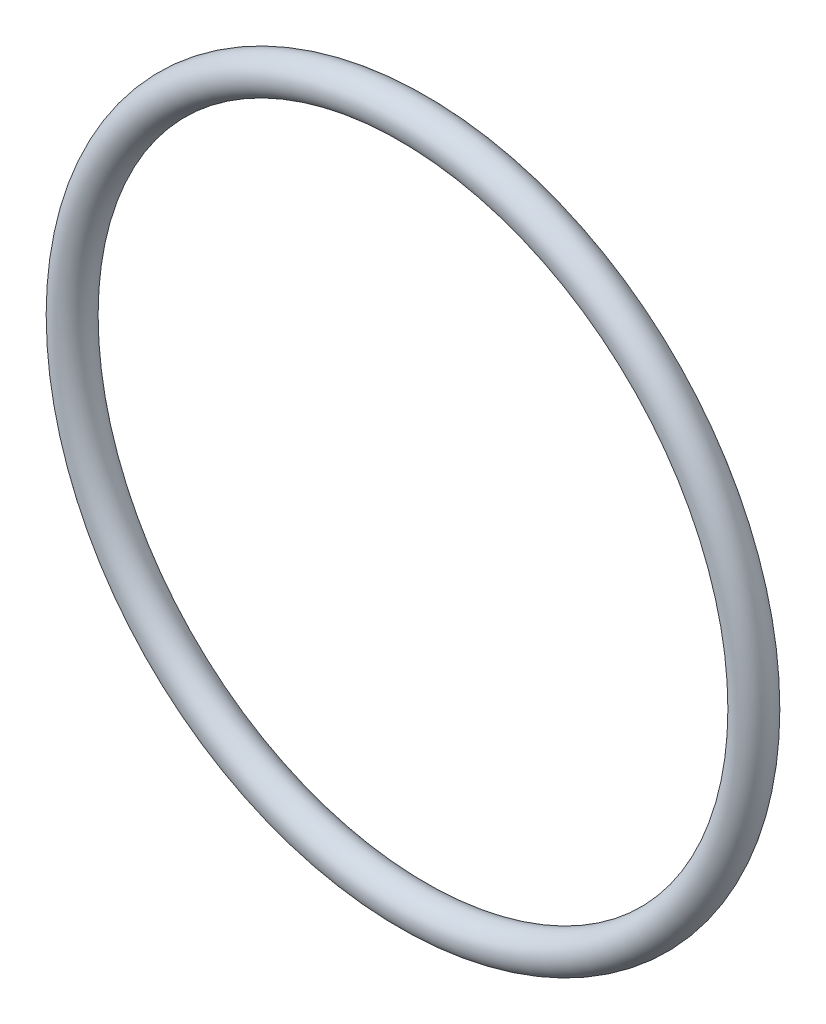
SolidWorks part; units mm, degrees
ref_plane "Front" through (0, 0, 0) normal (0, 0, 1) x (1, 0, 0)
ref_plane "Top" through (0, 0, 0) normal (0, 1, 0) x (1, 0, 0)
ref_plane "Right" through (0, 0, 0) normal (1, 0, 0) x (0, 0, -1)
sketch "Sketch1" plane through (0, 0, 0) normal (0, 0, 1) x (1, 0, 0)
  circle A0 centre (0, 0) radius 27.2
  dimension "d1" = 54.4
sketch "Sketch2" plane through (0, 0, 0) normal (0, 1, 0) x (1, 0, 0)
  circle A0 centre (-28.75, 0) radius 1.55
  point P2 (-27.2, 0)
  dimension "d2" = 3.1
sweep "Sweep1" add profiles "Sketch2" path "Sketch1"
ref_axis "Axis1" through (0, 0, -4.8575) along (0, 0, 1)
